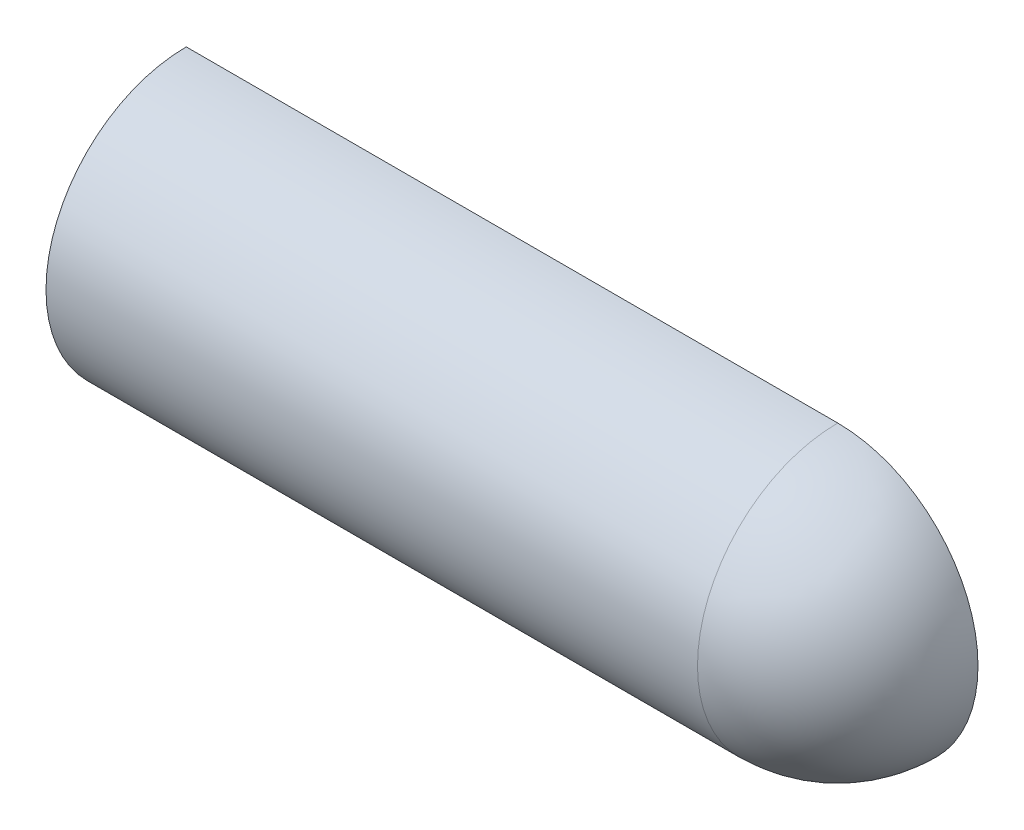
SolidWorks part; units mm, degrees
ref_plane "Front Plane" through (0, 0, 0) normal (0, 0, 1) x (1, 0, 0)
ref_plane "Top Plane" through (0, 0, 0) normal (0, 1, 0) x (1, 0, 0)
ref_plane "Right Plane" through (0, 0, 0) normal (1, 0, 0) x (0, 0, -1)
sketch "Sketch2" plane through (0, 0, 0) normal (0, 0, 1) x (1, 0, 0)
  line L0 (26, 0) -> (31, 0)
  line L2 (-144, 31) -> (0, 31)
  line L3 (-144, 31) -> (-144, 26)
  line L4 (0, 26) -> (-144, 26)
  arc A0 (-27.2886, -14.7083) -> (27.2886, 14.7083) centre (0, 0) ccw construction
  circle A1 centre (0, 0) radius 31 construction
  arc A2 (0, 31) -> (0, -31) centre (0, 0) ccw construction
  arc A3 (31, 0) -> (0, 31) centre (0, 0) ccw
  arc A4 (26, 0) -> (0, 26) centre (0, 0) ccw
revolve "Revolve1" add sketch "Sketch2" angle 180 about L0
